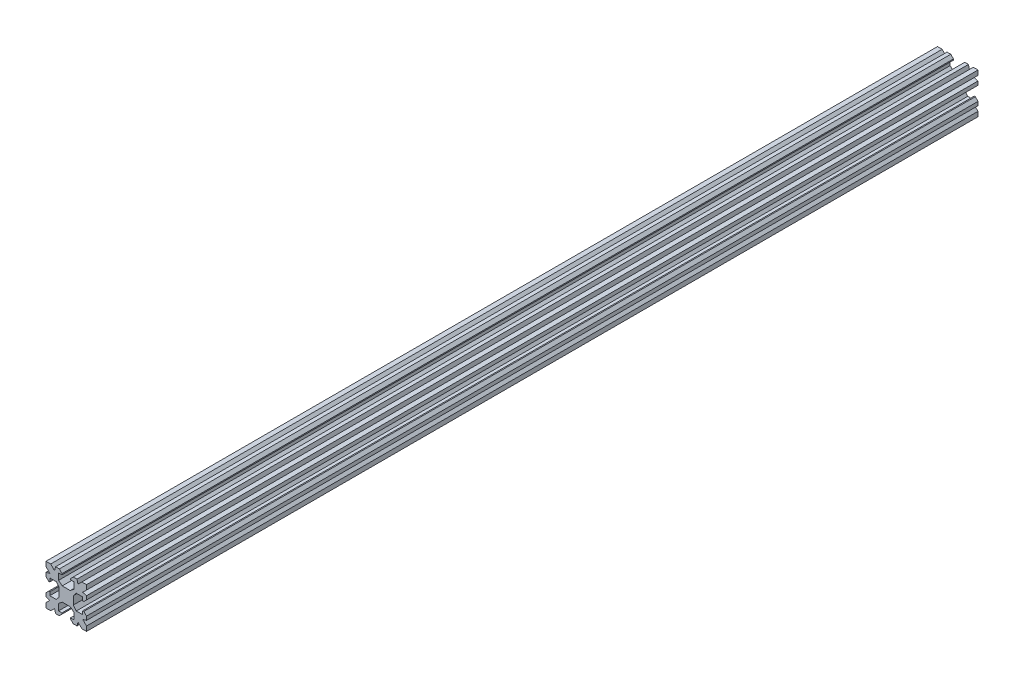
SolidWorks part; units mm, degrees
ref_plane "Спереди" through (0, 0, 0) normal (0, 0, 1) x (1, 0, 0)
ref_plane "Сверху" through (0, 0, 0) normal (0, 1, 0) x (1, 0, 0)
ref_plane "Справа" through (0, 0, 0) normal (1, 0, 0) x (0, 0, -1)
sketch "Эскиз1" plane through (0, 0, 0) normal (0, 0, 1) x (1, 0, 0)
  line L0 (1.58, 6.1) -> (2.85, 6.1)
  line L1 (-7.5, -7.5) -> (7.5, -7.5)
  line L2 (-7.5, -7.5) -> (-7.5, 7.5)
  line L3 (-7.5, 7.5) -> (7.5, 7.5)
  line L4 (7.5, -7.5) -> (7.5, 7.5)
  line L5 (-2.85, 6.1) -> (-1.58, 6.1)
  line L6 (-2.85, 6.1) -> (-2.85, 3.7)
  line L7 (-2.85, 3.7) -> (2.85, 3.7)
  line L8 (2.85, 6.1) -> (2.85, 3.7)
  line L9 (-2.85, 6.1) -> (2.85, 3.7) construction
  line L10 (-2.85, 3.7) -> (2.85, 6.1) construction
  line L11 (-1.58, 7.5) -> (1.58, 7.5)
  line L12 (-1.58, 7.5) -> (-1.58, 6.1)
  line L14 (1.58, 7.5) -> (1.58, 6.1)
  line L15 (-1.58, 7.5) -> (1.58, 6.1) construction
  line L16 (-1.58, 6.1) -> (1.58, 7.5) construction
  line L17 (6.1, -1.58) -> (6.1, -2.85)
  line L18 (6.1, 2.85) -> (6.1, 1.58)
  line L19 (6.1, 2.85) -> (3.7, 2.85)
  line L20 (3.7, 2.85) -> (3.7, -2.85)
  line L21 (6.1, -2.85) -> (3.7, -2.85)
  line L22 (7.5, 1.58) -> (7.5, -1.58)
  line L23 (7.5, 1.58) -> (6.1, 1.58)
  line L24 (7.5, -1.58) -> (6.1, -1.58)
  line L25 (6.1, 2.85) -> (3.7, -2.85) construction
  line L26 (3.7, 2.85) -> (6.1, -2.85) construction
  line L27 (7.5, 1.58) -> (6.1, -1.58) construction
  line L28 (6.1, 1.58) -> (7.5, -1.58) construction
  line L29 (-1.58, -6.1) -> (-2.85, -6.1)
  line L30 (2.85, -6.1) -> (1.58, -6.1)
  line L31 (2.85, -6.1) -> (2.85, -3.7)
  line L32 (2.85, -3.7) -> (-2.85, -3.7)
  line L33 (-2.85, -6.1) -> (-2.85, -3.7)
  line L34 (1.58, -7.5) -> (-1.58, -7.5)
  line L35 (1.58, -7.5) -> (1.58, -6.1)
  line L36 (-1.58, -7.5) -> (-1.58, -6.1)
  line L37 (2.85, -6.1) -> (-2.85, -3.7) construction
  line L38 (2.85, -3.7) -> (-2.85, -6.1) construction
  line L39 (1.58, -7.5) -> (-1.58, -6.1) construction
  line L40 (1.58, -6.1) -> (-1.58, -7.5) construction
  line L41 (-6.1, 1.58) -> (-6.1, 2.85)
  line L42 (-6.1, -2.85) -> (-6.1, -1.58)
  line L43 (-6.1, -2.85) -> (-3.7, -2.85)
  line L44 (-3.7, -2.85) -> (-3.7, 2.85)
  line L45 (-6.1, 2.85) -> (-3.7, 2.85)
  line L46 (-7.5, -1.58) -> (-7.5, 1.58)
  line L47 (-7.5, -1.58) -> (-6.1, -1.58)
  line L48 (-7.5, 1.58) -> (-6.1, 1.58)
  line L49 (-6.1, -2.85) -> (-3.7, 2.85) construction
  line L50 (-3.7, -2.85) -> (-6.1, 2.85) construction
  line L51 (-7.5, -1.58) -> (-6.1, 1.58) construction
  line L52 (-6.1, -1.58) -> (-7.5, 1.58) construction
  line L53 (-5.762, 7.5) -> (-4.342, 6.08)
  line L54 (-4.342, 6.08) -> (-3.962, 7.5)
  line L55 (-3.962, 7.5) -> (-5.762, 7.5)
  line L56 (-7.5, 7.5) -> (0, 0) construction
  line L57 (-6.08, 4.342) -> (-7.5, 3.962)
  line L58 (-7.5, 5.762) -> (-6.08, 4.342)
  line L59 (-7.5, 3.962) -> (-7.5, 5.762)
  line L60 (4.342, 6.08) -> (3.962, 7.5)
  line L61 (3.962, 7.5) -> (5.762, 7.5)
  line L62 (5.762, 7.5) -> (4.342, 6.08)
  line L63 (7.5, 3.962) -> (7.5, 5.762)
  line L64 (7.5, 5.762) -> (6.08, 4.342)
  line L65 (6.08, 4.342) -> (7.5, 3.962)
  line L66 (6.08, -4.342) -> (7.5, -3.962)
  line L67 (7.5, -3.962) -> (7.5, -5.762)
  line L68 (7.5, -5.762) -> (6.08, -4.342)
  line L69 (3.962, -7.5) -> (5.762, -7.5)
  line L70 (5.762, -7.5) -> (4.342, -6.08)
  line L71 (4.342, -6.08) -> (3.962, -7.5)
  line L72 (-4.342, -6.08) -> (-3.962, -7.5)
  line L73 (-3.962, -7.5) -> (-5.762, -7.5)
  line L74 (-5.762, -7.5) -> (-4.342, -6.08)
  line L75 (-7.5, -3.962) -> (-7.5, -5.762)
  line L76 (-7.5, -5.762) -> (-6.08, -4.342)
  line L77 (-6.08, -4.342) -> (-7.5, -3.962)
  point P0 (0, 0)
  point P5 (0, 4.9)
  point P12 (7.5, 0)
  point P13 (0, -7.5)
  point P14 (0, 6.8)
  point P19 (4.9, 0)
  point P26 (6.8, 0)
  point P31 (0, -4.9)
  point P36 (0, -6.8)
  point P41 (-4.9, 0)
  point P46 (-6.8, 0)
  point P51 (0, 0)
  point P77 (0, 0)
  dimension "D1" = 15
  dimension "D2" = 3.16
  dimension "D3" = 5.7
  dimension "D4" = 1.4
  dimension "D5" = 4
  dimension "D6" = 7.4
  dimension "D7" = 1.8
  dimension "D8" = 1.42
  dimension "D9" = 4
extrude "Бобышка-Вытянуть1" add sketch "Эскиз1" along normal blind 330 contours L77 L76 L2 L1 L74 L72 L36 L29 L33 L32 L31 L30 L35 L71 L70 L4 L68 L66 L24 L17 L21 L20 L19 L18 L23 L65 L64 L3 L62 L60 L14 L0 L8 L7 L6 L5 L12 L54 L53 L58 L57 region at (0, 0, 0)
sketch "Эскиз2" plane through (0, 0, 330) normal (0, 0, 1) x (1, 0, 0)
  line L0 (-3.7, 2.85) -> (-2.6, 1.5)
  line L1 (-2.6, 1.5) -> (-2.6, -1.5)
  line L2 (-2.6, -1.5) -> (-3.7, -2.85)
  line L3 (-3.7, -2.85) -> (-3.7, 2.85)
  line L4 (-7.5, -3.962) -> (-7.5, -1.58) construction
  line L5 (2.85, 3.7) -> (1.5, 2.6)
  line L6 (1.5, 2.6) -> (-1.5, 2.6)
  line L7 (-1.5, 2.6) -> (-2.85, 3.7)
  line L8 (-2.85, 3.7) -> (2.85, 3.7)
  line L9 (3.7, -2.85) -> (2.6, -1.5)
  line L10 (2.6, -1.5) -> (2.6, 1.5)
  line L11 (2.6, 1.5) -> (3.7, 2.85)
  line L12 (3.7, 2.85) -> (3.7, -2.85)
  line L13 (-2.85, -3.7) -> (-1.5, -2.6)
  line L14 (-1.5, -2.6) -> (1.5, -2.6)
  line L15 (1.5, -2.6) -> (2.85, -3.7)
  line L16 (2.85, -3.7) -> (-2.85, -3.7)
  point P6 (-2.6, 0)
  point P19 (0, 2.6)
  point P24 (2.6, 0)
  point P29 (0, -2.6)
  point P30 (0, 0)
  dimension "D1" = 3
  dimension "D2" = 4.9
  dimension "D3" = 4
extrude "Вырез-Вытянуть1" cut sketch "Эскиз2" against normal through all
chamfer "Фаска1" distance 1 angle 45 8 edges at (-7.5, 1.58, 165) (-7.5, -1.58, 165) (1.58, -7.5, 165) (-1.58, -7.5, 165) (7.5, -1.58, 165) (7.5, 1.58, 165) (1.58, 7.5, 165) (-1.58, 7.5, 165)
